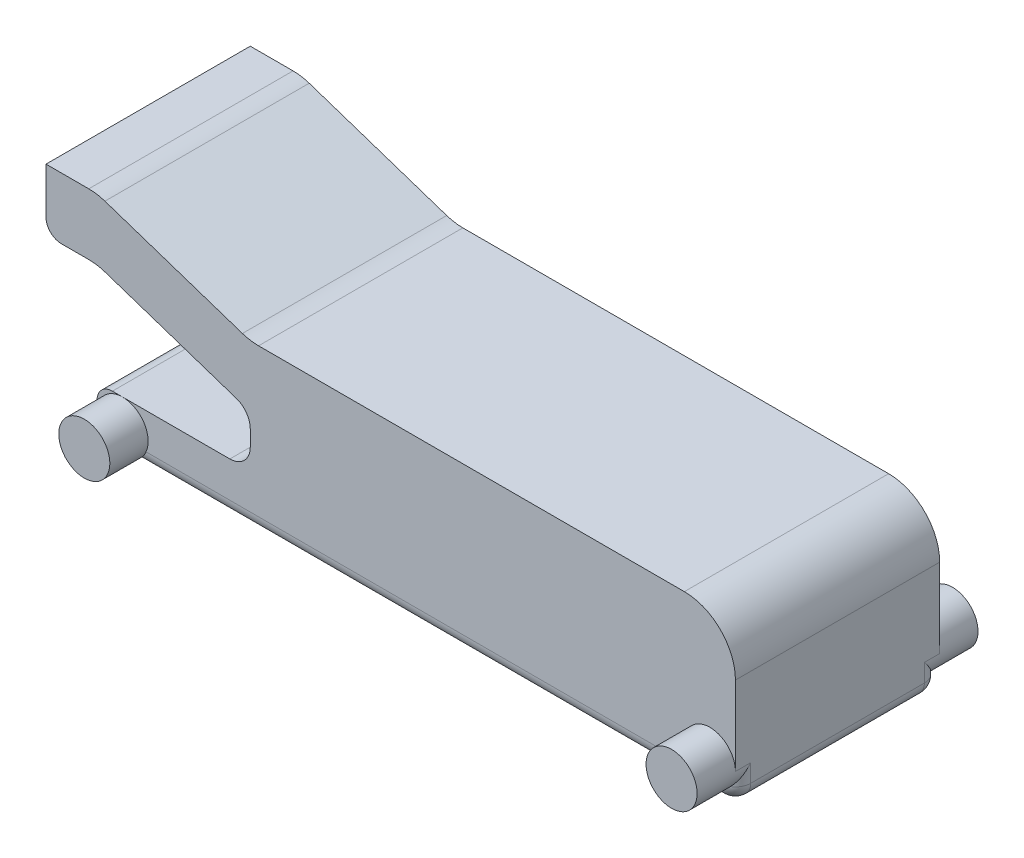
SolidWorks part; units mm, degrees
ref_plane "Alzado" through (0, 0, 0) normal (0, 0, 1) x (1, 0, 0)
ref_plane "Planta" through (0, 0, 0) normal (0, 1, 0) x (1, 0, 0)
ref_plane "Vista lateral" through (0, 0, 0) normal (1, 0, 0) x (0, 0, -1)
sketch "Croquis1" plane through (0, 0, 0) normal (0, 1, 0) x (1, 0, 0)
  line L1 (550, 200) -> (-700, 200)
  line L2 (550, 200) -> (550, -200)
  line L3 (550, -200) -> (-700, -200)
  line L4 (-700, 200) -> (-700, -200)
  dimension "D1" = 400
  dimension "D2" = 1250
  dimension "D3" = 550
  dimension "D4" = 200
extrude "Saliente-Extruir1" add sketch "Croquis1" along normal blind 100
sketch "Croquis2" plane through (0, 100, 0) normal (0, 1, 0) x (1, 0, 0)
  line L0 (-700, 200) -> (-700, -200) construction
  line L4 (-400, -200) -> (550, -200)
  line L5 (-400, -200) -> (-400, 200)
  line L6 (-400, 200) -> (550, 200)
  line L7 (550, -200) -> (550, 200)
  dimension "D1" = 300
  dimension "D2" = 400
  dimension "D3" = 950
  dimension "D4" = 200
extrude "Saliente-Extruir2" add sketch "Croquis2" along normal blind 220
fillet "Redondeo1" radius 100 1 edges at (550, 320, 0)
sketch "Croquis3" plane through (0, 0, 200) normal (0, 0, 1) x (1, 0, 0)
  line L0 (-400, 320) -> (-700, 420)
  line L1 (-700, 420) -> (-800, 420)
  line L2 (-800, 420) -> (-800, 300)
  line L3 (-800, 300) -> (-700, 300)
  line L4 (-700, 300) -> (-400, 200)
  line L5 (-400, 320) -> (-400, 100) construction
  line L6 (-400, 200) -> (-400, 320)
  line L7 (-700, 100) -> (-700, 0) construction
  line L8 (-700, 420) -> (-700, 300) construction
  line L9 (-700, 100) -> (-400, 100) construction
  dimension "D1" = 100
  dimension "D2" = 120
  dimension "D3" = 100
  dimension "D4" = 200
extrude "Saliente-Extruir3" add sketch "Croquis3" against normal blind 400
fillet "Redondeo2" radius 40 1 edges at (-400, 100, 0)
fillet "Redondeo3" radius 40 1 edges at (-400, 200, 0)
fillet "Redondeo4" radius 100 1 edges at (-700, 300, 0)
fillet "Redondeo5" radius 100 1 edges at (-400, 320, 0)
fillet "Redondeo6" radius 100 1 edges at (-700, 420, 0)
sketch "Croquis4" plane through (0, 320, 0) normal (0, 1, 0) x (1, 0, 0)
  line L0 (550, 200) -> (550, -200) construction
  line L1 (-120, 200) -> (220, 200)
  line L2 (-120, 200) -> (-120, -200)
  line L3 (-120, -200) -> (220, -200)
  line L4 (220, 200) -> (220, -200)
  dimension "D1" = 340
  dimension "D2" = 400
  dimension "D3" = 200
  dimension "D4" = 330
sketch "Croquis5" plane through (0, 0, 200) normal (0, 0, 1) x (1, 0, 0)
  line L0 (-700, 100) -> (-440, 100) construction
  line L1 (-700, 100) -> (-700, 0) construction
  line L2 (550, 220) -> (550, 0) construction
  line L4 (-700, 0) -> (550, 0) construction
  circle A0 centre (500, 65) radius 50
  circle A1 centre (-650, 50) radius 50
  dimension "D2" = 100
  dimension "D4" = 100
  dimension "D1" = 50
  dimension "D3" = 50
  dimension "D5" = 50
  dimension "D6" = 65
extrude "Saliente-Extruir4" add sketch "Croquis5" along normal blind 75
sketch "Croquis6" plane through (0, 0, -200) normal (0, 0, -1) x (1, 0, 0)
  line L0 (550, 0) -> (-700, 0) construction
  line L1 (-700, -100) -> (-700, 0) construction
  line L2 (550, -220) -> (550, 0) construction
  circle A0 centre (-650, -50) radius 50
  circle A1 centre (500, -65) radius 50
  dimension "D1" = 100
  dimension "D6" = 100
  dimension "D2" = 50
  dimension "D3" = 50
  dimension "D4" = 50
  dimension "D5" = 65
extrude "Saliente-Extruir5" add sketch "Croquis6" along normal blind 75
fillet "Redondeo9" radius 30 1 edges at (-700, 0, 0)
fillet "Redondeo10" radius 30 1 edges at (-700, 100, 0)
fillet "Redondeo11" radius 30 1 edges at (550, 0, 0)
fillet "Redondeo12" radius 30 1 edges at (-800, 300, 0)
fillet "Redondeo13" radius 30 3 edges at (541.2132, 8.7868, 200) (550, 47.5, 200) (-65, 0, 200)
fillet "Redondeo14" radius 30 3 edges at (550, 47.5, -200) (-65, 0, -200) (541.2132, 8.7868, -200)
